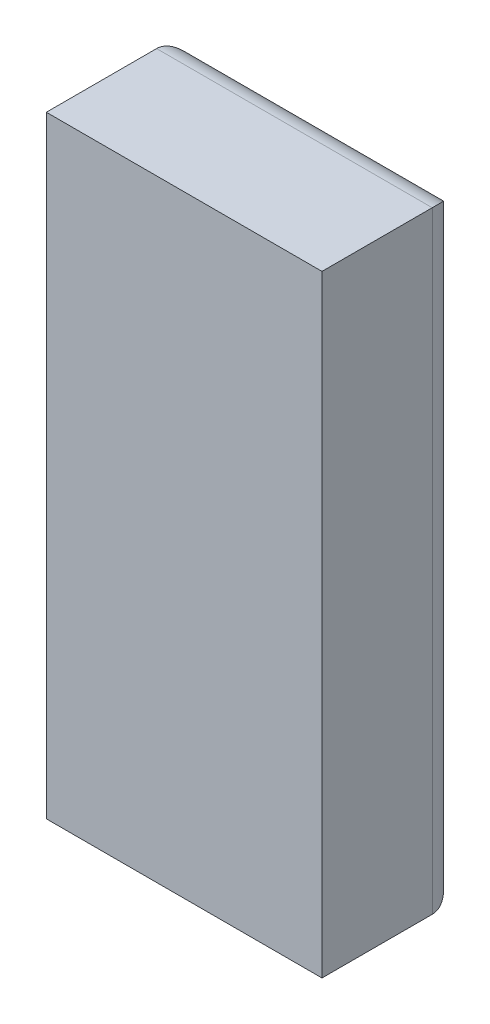
SolidWorks part; units mm, degrees
ref_plane "Front Plane" through (0, 0, 0) normal (0, 0, 1) x (1, 0, 0)
ref_plane "Top Plane" through (0, 0, 0) normal (0, 1, 0) x (1, 0, 0)
ref_plane "Right Plane" through (0, 0, 0) normal (1, 0, 0) x (0, 0, -1)
sketch "Profile" plane through (0, 0, 0) normal (0, 0, 1) x (1, 0, 0)
  line L1 (-50, 111) -> (50, 111)
  line L2 (-50, 111) -> (-50, -111)
  line L3 (-50, -111) -> (50, -111)
  line L4 (50, 111) -> (50, -111)
  line L5 (-50, 111) -> (50, -111) construction
  line L6 (-50, -111) -> (50, 111) construction
  point P0 (0, 0)
  dimension "D1" = 100
  dimension "D2" = 222
extrude "Profile Extrude" add sketch "Profile" against normal blind 50
fillet "Fillet1" radius 10 4 edges at (0, 111, -50) (-50, 0, -50) (0, -111, -50) (50, 0, -50)
